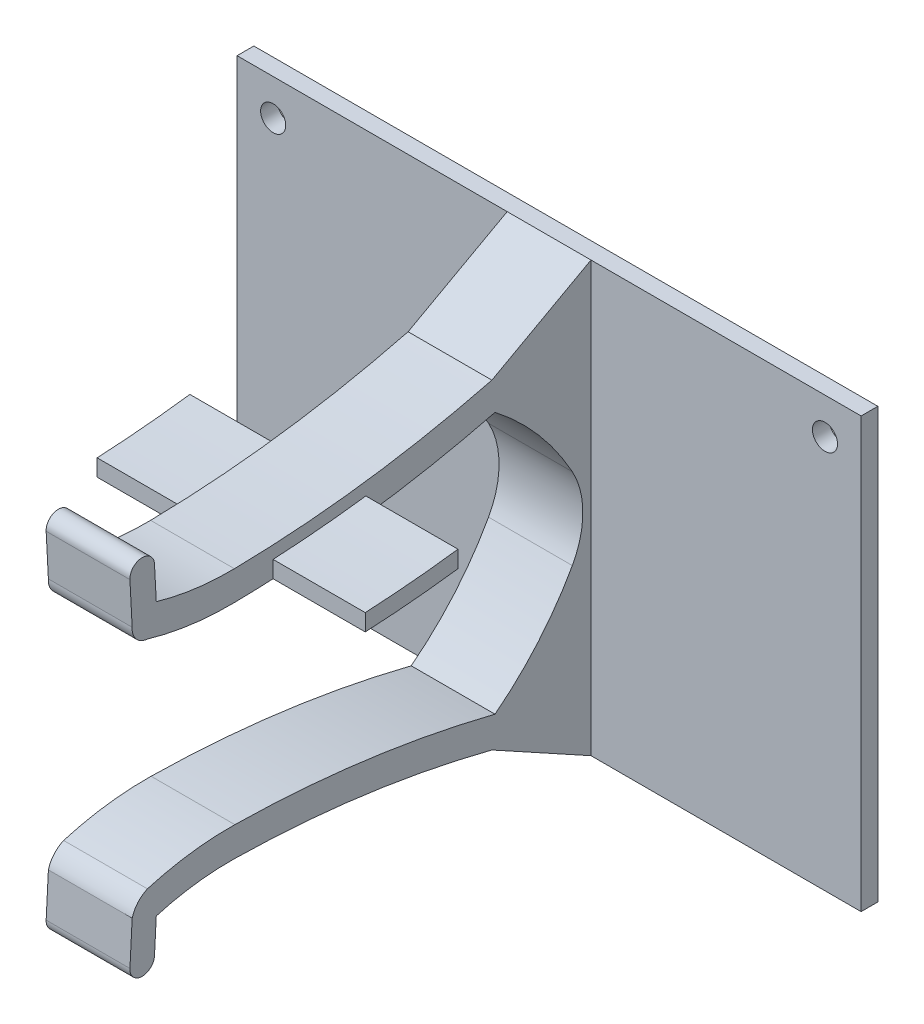
SolidWorks part; units mm, degrees
ref_plane "Front Plane" through (0, 0, 0) normal (0, 0, 1) x (1, 0, 0)
ref_plane "Top Plane" through (0, 0, 0) normal (0, 1, 0) x (1, 0, 0)
ref_plane "Right Plane" through (0, 0, 0) normal (1, 0, 0) x (0, 0, -1)
sketch "Sketch1" plane through (0, 0, 0) normal (0, 0, 1) x (1, 0, 0)
  line L0 (-32.93, 0) -> (32.93, 0) construction
  line L1 (-32.93, 4.3095) -> (32.93, 4.3095)
  line L3 (1.941, -42.566) -> (1.941, 0) construction
  line L4 (-37.2395, 4.3095) -> (37.2395, 4.3095)
  line L5 (-37.2395, 4.3095) -> (-37.2395, -46.9281)
  line L6 (-37.2395, -46.9281) -> (37.2395, -46.9281)
  line L7 (37.2395, 4.3095) -> (37.2395, -46.9281)
  circle A0 centre (1.941, -42.566) radius 1.5
  circle A1 centre (-32.93, 0) radius 1.5
  circle A2 centre (32.93, 0) radius 1.5
  point P0 (-32.93, 0)
  point P1 (32.93, 0)
  point P2 (1.941, 0)
  point P4 (1.941, -42.566)
  point P11 (0, 0)
  point P16 (1.941, -21.283)
  dimension "D1" = 32.93
  dimension "D2" = 32.93
  dimension "D3" = 34.871
  dimension "D4" = 42.566
extrude "Boss-Extrude1" add sketch "Sketch1" along normal blind 2 contours L7 L4 L1 L5 L6 A2 A1 A0 region at (-0.0036, -21.3491, 0)
sketch "Sketch2" plane through (0, 0, 0) normal (1, 0, 0) x (0, 0, -1)
  line L0 (-2, 4.3095) -> (-2, -46.9281) construction
  line L1 (-13.8279, -2.1937) -> (-2, 4.3095)
  line L2 (-56.7607, -6.2762) -> (-57.0286, -1.2111)
  line L3 (-2, 4.3095) -> (0, 4.3095)
  line L4 (0, 4.3095) -> (0, -46.9281)
  line L5 (0, -46.9281) -> (-2, -46.9281)
  line L7 (-13.8279, -40.4249) -> (-2, -46.9281)
  line L8 (-53.8846, -37.5543) -> (-54.0966, -41.5625)
  line L9 (-56.7607, -36.3424) -> (-57.0286, -41.4075)
  line L12 (-53.8846, -5.0643) -> (-54.0966, -1.0561)
  arc A0 (-44.5616, -36.2995) -> (-13.8279, -40.4249) centre (-46.6985, -168.7607) cw
  arc A1 (-4.2258, -26.1591) -> (-4.2258, -16.4595) centre (-12.9711, -21.3093) ccw
  arc A2 (-44.5616, -36.2995) -> (-53.8846, -37.5543) centre (-45.0695, -67.7869) ccw
  arc A3 (-54.0966, -41.5625) -> (-57.0286, -41.4075) centre (-55.5626, -41.485) cw
  arc A4 (-13.4557, -5.7103) -> (-4.2258, -16.4595) centre (-34.9308, -33.4873) cw
  arc A5 (-54.9419, -8.4017) -> (-56.7607, -6.2762) centre (-54.7885, -6.4295) cw
  arc A6 (-54.9419, -34.2169) -> (-56.7607, -36.3424) centre (-53.619, -37.1899) ccw
  arc A7 (-44.5616, -6.3192) -> (-53.8846, -5.0643) centre (-45.0695, 25.1682) cw
  arc A9 (-13.4557, -36.9083) -> (-4.2258, -26.1591) centre (-34.9308, -9.1313) ccw
  arc A10 (-44.5616, -6.3192) -> (-13.8279, -2.1937) centre (-46.6985, 126.142) ccw
  arc A12 (-44.5051, -9.8187) -> (-54.9419, -8.4017) centre (-45.0696, 25.1682) cw
  arc A13 (-54.0966, -1.0561) -> (-57.0286, -1.2111) centre (-55.5626, -1.1336) ccw
  arc A14 (-44.5051, -9.8187) -> (-13.4557, -5.7103) centre (-46.6985, 126.142) ccw
  arc A15 (-44.5052, -32.7999) -> (-54.9419, -34.2169) centre (-45.0696, -67.7869) ccw
  arc A16 (-44.5052, -32.7999) -> (-13.4557, -36.9083) centre (-46.6985, -168.7607) cw
  point P0 (-2, -21.3093)
  point P1 (-44, -21.3081)
  point P4 (-44.5293, -8.3189)
  point P5 (-44, -34.3081)
  point P6 (-2, -34.3093)
  point P7 (-2, -8.3093)
  point P8 (-2, -0.6905)
  point P9 (-2, -41.9281)
  point P10 (-44.5293, -8.3189)
  point P13 (-46.6985, 126.142)
  point P14 (-2, -0.6905)
  point P31 (-56.1047, -8.8246)
  point P35 (-54.8298, -4.7726)
  point P46 (-55.4287, -3.6662)
  point P56 (-44.5374, -7.819)
  point P58 (-45.0695, 25.1682)
  point P60 (-55.2947, -6.1987)
  dimension "D6" = 10
  dimension "D1" = 42
  dimension "D2" = 13
  dimension "D3" = 13
  dimension "D4" = 5
  dimension "D5" = 5
extrude "Boss-Extrude2" add sketch "Sketch2" along normal blind 5 and the other way blind 5
sketch "Sketch5" plane through (0, 0, 0) normal (1, 0, 0) x (0, 0, -1)
  line L0 (-39.9419, -7.6659) -> (-39.9419, -9.6684)
  line L1 (-28.874, -6.6454) -> (-28.8617, -8.6615)
  arc A0 (-39.9419, -7.6659) -> (-28.874, -6.6454) centre (-46.6985, 126.142) ccw
  arc A2 (-39.9419, -9.6684) -> (-28.8617, -8.6615) centre (-46.6985, 126.142) ccw
  arc A3 (-44.5051, -9.8187) -> (-13.4557, -5.7103) centre (-46.6985, 126.142) ccw construction
  point P0 (0, 0)
extrude "Boss-Extrude3" add sketch "Sketch5" along normal blind 16 and the other way blind 16
